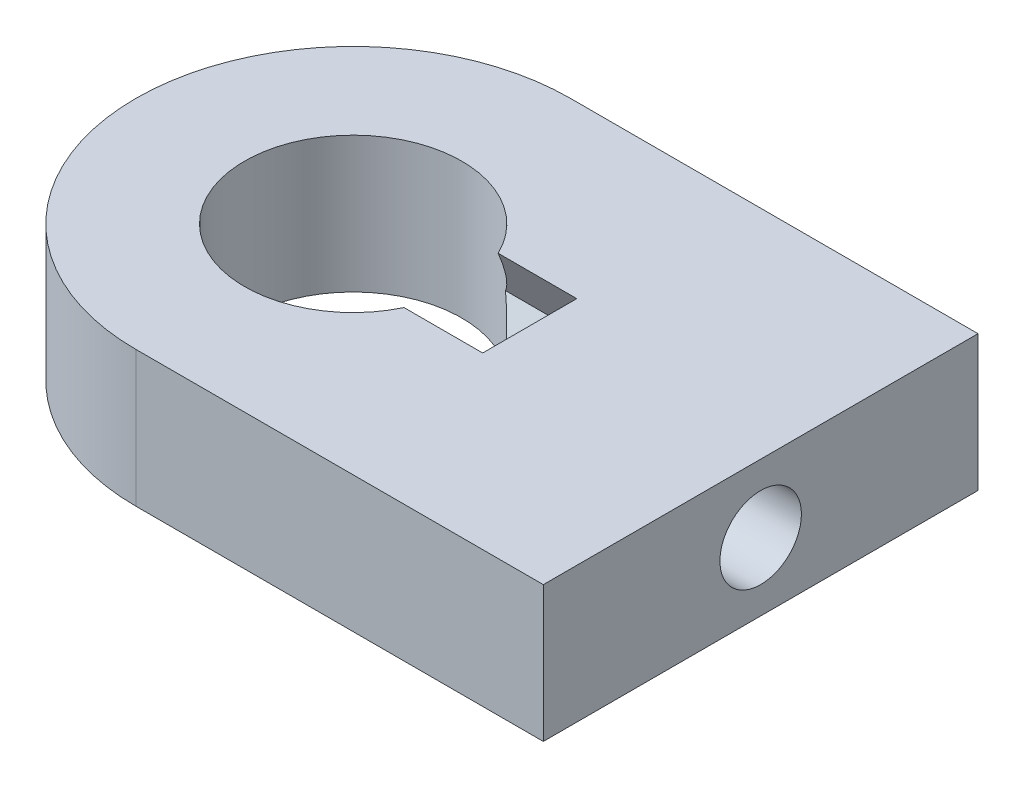
SolidWorks part; units mm, degrees
material "ABS"
ref_plane "Front Plane" through (0, 0, 0) normal (0, 0, 1) x (1, 0, 0)
ref_plane "Top Plane" through (0, 0, 0) normal (0, 1, 0) x (1, 0, 0)
ref_plane "Right Plane" through (0, 0, 0) normal (1, 0, 0) x (0, 0, -1)
sketch "Sketch1" plane through (0, 0, 0) normal (0, 1, 0) x (1, 0, 0)
  line L0 (0, 8) -> (15, 8)
  line L1 (15, 8) -> (15, -8)
  line L2 (15, -8) -> (0, -8)
  circle A0 centre (0, 0) radius 4
  arc A1 (0, -8) -> (0, 8) centre (0, 0) cw
  dimension "D1" = 8
  dimension "D2" = 8
  dimension "D3" = 15
extrude "Boss-Extrude1" add sketch "Sketch1" along normal blind 5
sketch "Sketch2" plane through (15, 0, 0) normal (1, 0, 0) x (0, 0, -1)
  line L0 (0, -3.0185) -> (0, 8.0813) construction
  line L1 (3.1754, 2.5) -> (1.5877, 5.25)
  line L2 (1.5877, 5.25) -> (-1.5877, 5.25)
  line L3 (-1.5877, 5.25) -> (-3.1754, 2.5)
  line L4 (-3.1754, 2.5) -> (-1.5877, -0.25)
  line L5 (-1.5877, -0.25) -> (1.5877, -0.25)
  line L6 (1.5877, -0.25) -> (3.1754, 2.5)
  line L7 (-8, 2.5) -> (8, 2.5) construction
  line L9 (-8, 5) -> (-8, 0) construction
  line L10 (8, 5) -> (8, 0) construction
  circle A0 centre (0, 2.5) radius 2.75 construction
  circle A1 centre (0, 2.5) radius 1.5
  dimension "D1" = 5.5
  dimension "D2" = 3
extrude "Cut-Extrude1" cut sketch "Sketch2" against normal up to next contours A1 region at (15, 2.5, 0)
sketch "Sketch3" plane through (0, 5, 0) normal (0, 1, 0) x (1, 0, 0)
  line L0 (6.5, 9.4882) -> (6.5, -10.0981) construction
  line L1 (0, -8) -> (15, -8) construction
  circle A0 centre (0, 0) radius 4 construction
  point P4 (6.5, -8)
  dimension "D1" = 6.5
extrude "Cut-Extrude2" cut sketch "Sketch2<4>" against normal up to next from vertex starting at point (6.5, 5, 8)
sketch "Sketch2<4>" plane through (15, 0, 0) normal (1, 0, 0) x (0, 0, -1) same geometry as "Sketch2"
equation "\"rod_diameter\"= 8"
equation "\"rod_hole_thickness\"= 4"
equation "\"rod_radius\"= \"rod_diameter\" / 2"
equation "\"platter_diameter\"= 320"
equation "\"platter_radius\"= \"platter_diameter\" / 2"
equation "\"extruder_mount_hole_spacing\"= 75"
equation "\"arm_rod_spacing\"= 40"
equation "\"top_frame_rod_spacing\"= \"arm_rod_spacing\" + 40"
equation "\"motor_level_rod_spacing\"= 15"
equation "\"linear_bearing_diameter\"= 15"
equation "\"z_rod_spacing\"= 75"
equation "\"platter_rod_spacing\"= 50"
equation "\"rod_nut_thickness\"= 6.5"
equation "\"rod_nut_inscribed_diameter\"= 13"
equation "\"z_height\"= 350"
equation "\"gear_pitch\"=2"
equation "\"r_gear_teeth\"= 450"
equation "\"theta_gear_teeth\"= 385"
equation "\"D1@Sketch1\"= \"rod_diameter\""
equation "\"D2@Sketch1\"=\"rod_radius\"+\"rod_hole_thickness\""
equation "\"D1@Sketch3\"=\"rod_radius\"+2.5"
